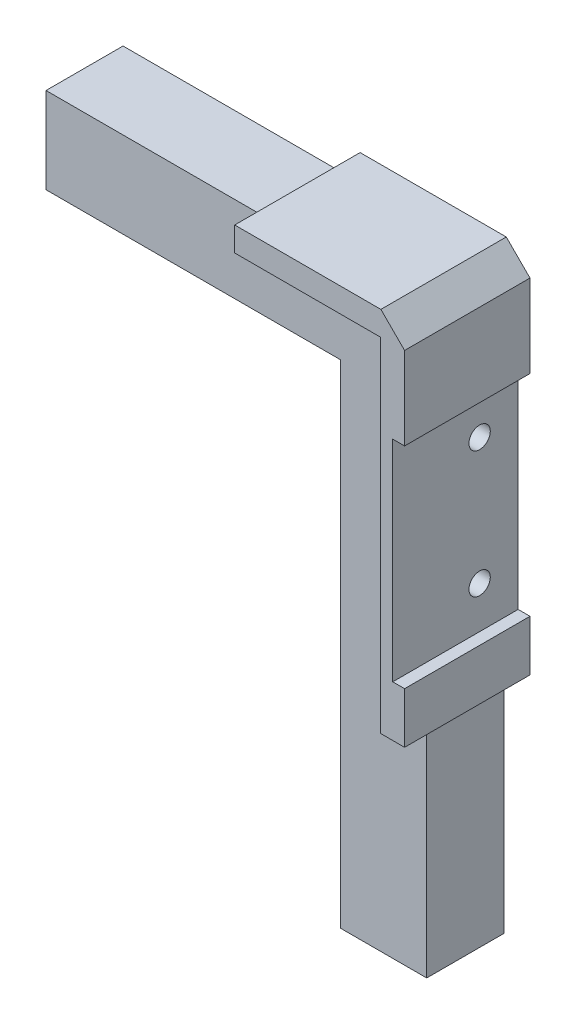
SolidWorks part; units mm, degrees
ref_plane "Front Plane" through (0, 0, 0) normal (0, 0, 1) x (1, 0, 0)
ref_plane "Top Plane" through (0, 0, 0) normal (0, 1, 0) x (1, 0, 0)
ref_plane "Right Plane" through (0, 0, 0) normal (1, 0, 0) x (0, 0, -1)
ref_plane "PZ 20.375" through (0, 0, 20.375) normal (0, 0, 1) x (1, 0, 0)
sketch "body and tongues sketch" plane through (0, 0, 20.375) normal (0, 0, 1) x (1, 0, 0)
  line L0 (3.42, 3.07) -> (0.42, 6.07)
  line L1 (0.42, 6.07) -> (-18.08, 6.07)
  line L2 (-18.08, 6.07) -> (-18.08, 2.75)
  line L3 (-18.08, 2.75) -> (-48.08, 2.75)
  line L4 (-48.08, 2.75) -> (-48.08, -8.13)
  line L5 (-48.08, -8.13) -> (-10.78, -8.13)
  line L6 (-10.78, -8.13) -> (-10.78, -70.43)
  line L7 (-10.78, -70.43) -> (0.1, -70.43)
  line L8 (0.1, -70.43) -> (0.1, -40.43)
  line L9 (0.1, -40.43) -> (3.42, -40.43)
  line L10 (3.42, -40.43) -> (3.42, 3.07)
extrude "body and tongues" add sketch "body and tongues sketch" along normal mid plane 9.75
ref_plane "PZ 23.435" through (0, 0, 23.435) normal (0, 0, 1) x (1, 0, 0)
sketch "rim sketch" plane through (0, 0, 23.435) normal (0, 0, 1) x (1, 0, 0)
  line L0 (3.42, 3.07) -> (0.42, 6.07)
  line L1 (0.42, 6.07) -> (-18.08, 6.07)
  line L2 (-18.08, 6.07) -> (-18.08, 3)
  line L3 (-18.08, 3) -> (0.35, 3)
  line L4 (0.35, 3) -> (0.35, -40.43)
  line L5 (0.35, -40.43) -> (3.42, -40.43)
  line L6 (3.42, -40.43) -> (3.42, 3.07)
extrude "rim" add sketch "rim sketch" along normal mid plane 15.87
sketch "bracket seat sketch" plane through (0, 0, 23.435) normal (0, 0, 1) x (1, 0, 0)
  line L0 (1.92, -34) -> (4.42, -34)
  line L1 (4.42, -34) -> (4.42, -7.4)
  line L2 (4.42, -7.4) -> (1.92, -7.4)
  line L3 (1.92, -7.4) -> (1.92, -34)
extrude "bracket seat" cut sketch "bracket seat sketch" against normal mid plane 17.87
ref_plane "PX -2.580" through (-2.58, 0, 0) normal (1, 0, 0) x (0, 0, -1)
sketch "screw pilots sketch" plane through (-2.58, 0, 0) normal (1, 0, 0) x (0, 0, -1)
  circle A0 centre (-20.375, -28.7) radius 1.35
  circle A1 centre (-20.375, -12.7) radius 1.35
extrude "screw pilots" cut sketch "screw pilots sketch" against normal mid plane 11
equation "\"diffL\" = 608.8mm"
equation "\"diffW\" = 329.4mm"
equation "\"diffT\" = 2.9mm"
equation "\"chanSlotW\" = 12.9mm"
equation "\"chanSlotDepth\" = 11.13mm"
equation "\"chanFloor\" = 1.57mm"
equation "\"chanLeg\" = 12.7mm"
equation "\"lightL\" = 605mm"
equation "\"lightW\" = 331mm"
equation "\"lightH\" = 92mm"
equation "\"lightSideFlat\" = 30mm"
equation "\"lightSlopeLen\" = 33.1mm"
equation "\"lightWingDepth\" = 47.9mm"
equation "\"lightWingFlat\" = 90.2mm"
equation "\"lightChanW\" = 99.6mm"
equation "\"lightChanStand\" = 44.1mm"
equation "\"insFlangeD\" = 12.3mm"
equation "\"insFromEnd\" = 20.7mm"
equation "\"insUpSlope\" = 20.8mm"
equation "\"gaugeH\" = 10mm"
equation "\"gaugeStepLen\" = 14mm"
equation "\"gaugeStepW0\" = 13.1mm"
equation "\"gaugeStepDW\" = 0.2mm"
equation "\"gaugeSteps\" = 5mm"
equation "\"gaugeHandleLen\" = 30mm"
equation "\"gaugeHandleW\" = 24mm"
equation "\"gaugeSlot0\" = 3mm"
equation "\"gaugeSlotD\" = 0.1mm"
equation "\"gaugeSlotDepth\" = 8mm"
equation "\"gap\" = 25.4mm"
equation "\"edgeL\" = 1mm"
equation "\"edgeW\" = 0.75mm"
equation "\"proud\" = 1.5mm"
equation "\"seatClr\" = 0.15mm"
equation "\"tongueClrZ\" = 0.1mm"
equation "\"tongueClrX\" = 0.25mm"
equation "\"tongueLen\" = 30mm"
equation "\"armSide\" = 45mm"
equation "\"armEnd\" = 20mm"
equation "\"cornerCham\" = 3mm"
equation "\"brkW\" = 26mm"
equation "\"brkT\" = 7mm"
equation "\"brkSeatClr\" = 0.2mm"
equation "\"brkScrewSpan\" = 16mm"
equation "\"pilotD\" = 2.7mm"
equation "\"pilotDepth\" = 10mm"
equation "\"screwClrD\" = 3.9mm"
equation "\"jogBelow\" = 4mm"
equation "\"padT\" = 7mm"
equation "\"padLen\" = 31mm"
equation "\"m6Clr\" = 7mm"
equation "\"m6Slot\" = 3mm"
equation "\"flangeRelD\" = 17mm"
equation "\"flangeRelDepth\" = 1.5mm"
equation "\"relLen\" = 7mm"
equation "\"relDepth\" = 4mm"
equation "\"relLand\" = 2mm"
equation "\"knockN\" = 100mm"
equation "\"petgcfE\" = 3000mm"
equation "\"mockExtent\" = 110mm"
equation "\"relZnear\" = 9.4mm"
equation "\"relZfar\" = 23.4mm"
equation "\"headD\" = 8mm"
equation "\"headH\" = 2.5mm"
equation "\"headFromEnd\" = 6.8mm"
equation "\"headBack\" = 16.4mm"
equation "\"sideClr\" = 0.4mm"
